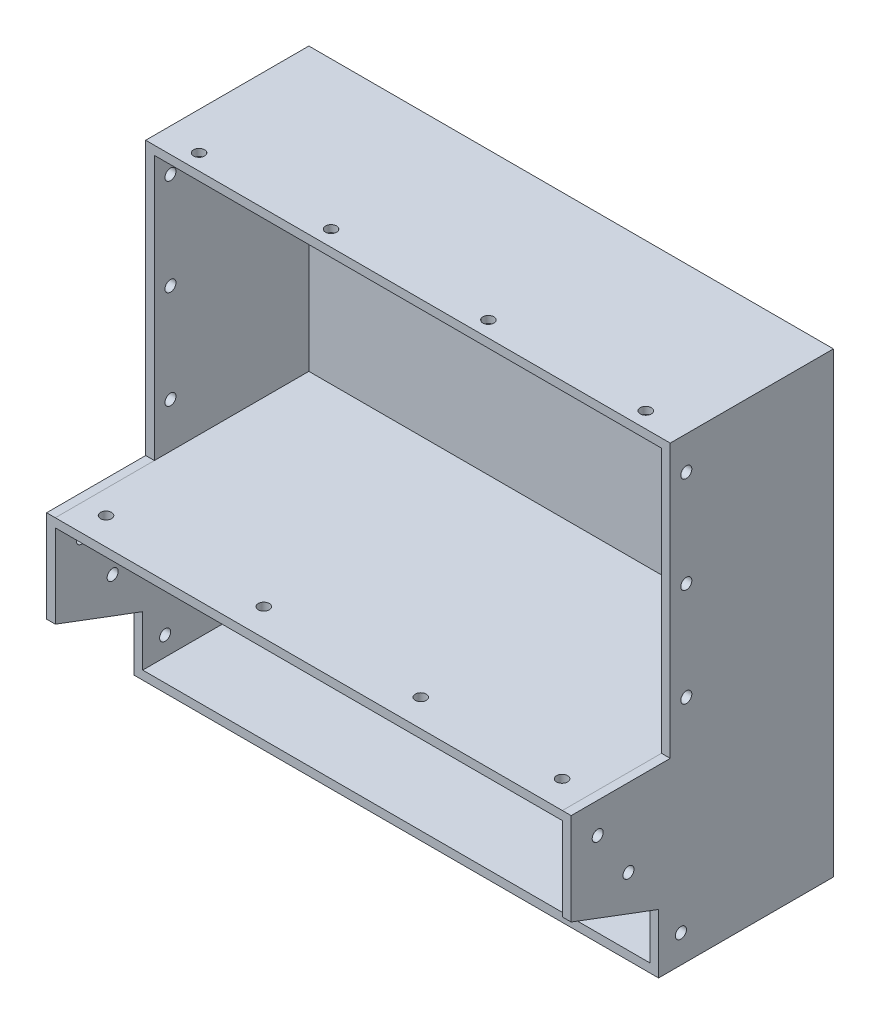
SolidWorks part; units mm, degrees
material "Custom Plastic"
ref_plane "X-Y Datum" through (0, 0, 0) normal (0, 0, 1) x (1, 0, 0)
ref_plane "X-Z Datum" through (0, 0, 0) normal (0, 1, 0) x (1, 0, 0)
ref_plane "Y-Z Datum" through (0, 0, 0) normal (1, 0, 0) x (0, 0, -1)
sketch "Sketch1" plane through (0, 0, 0) normal (0, 0, 1) x (1, 0, 0)
  line L1 (-95.25, -83.058) -> (95.25, -83.058)
  line L2 (-95.25, -83.058) -> (-95.25, 83.058)
  line L3 (-95.25, 83.058) -> (95.25, 83.058)
  line L4 (95.25, -83.058) -> (95.25, 83.058)
  line L5 (-95.25, -83.058) -> (95.25, 83.058) construction
  line L6 (-95.25, 83.058) -> (95.25, -83.058) construction
  point P0 (0, 0)
  dimension "D1" = 166.116
  dimension "D2" = 190.5
extrude "Boss-Extrude1" add sketch "Sketch1" along normal blind 95.25
sketch "Sketch3" plane through (0, 0, 95.25) normal (0, 0, 1) x (1, 0, 0)
  line L0 (-92.075, -49.9618) -> (92.075, -49.9618)
  line L1 (92.075, -61.8913) -> (95.25, -61.8913)
  line L2 (-92.075, -61.8913) -> (92.075, -61.8913)
  line L3 (95.25, -83.058) -> (95.25, 83.058) construction
  line L4 (-92.075, -61.8913) -> (-92.075, -79.883)
  line L5 (-95.25, -49.9618) -> (-95.25, -61.8913)
  line L6 (92.075, -61.8913) -> (92.075, -79.883)
  line L7 (-95.25, 83.058) -> (-95.25, -83.058) construction
  line L8 (-122.0928, 3.2687) -> (-122.1486, 3.2687)
  line L9 (92.075, -79.883) -> (76.2531, -79.883)
  line L13 (-95.25, 32.8917) -> (-92.075, 32.8917)
  line L15 (-122.0786, -16.0951) -> (-122.1486, -16.0951)
  line L17 (95.25, -49.9618) -> (92.075, -49.9618)
  line L18 (-92.075, -79.883) -> (76.2531, -79.883)
  line L21 (-92.075, -49.9618) -> (-95.25, -49.9618)
  line L23 (-81.0858, 79.883) -> (83.8833, 79.883)
  line L25 (-81.0858, 79.883) -> (-92.075, 79.883)
  line L26 (-92.075, 79.883) -> (-92.075, -16.0951)
  line L28 (95.25, 48.6627) -> (92.075, 48.6627)
  line L30 (83.8833, 79.883) -> (92.075, 79.883)
  line L31 (92.075, 79.883) -> (92.075, -16.0951)
  line L33 (-92.075, -16.0951) -> (92.075, -16.0951)
  line L34 (95.25, -49.9618) -> (95.25, -61.8913)
  line L35 (-95.25, -61.8913) -> (-92.075, -61.8913)
extrude "Cut-Extrude1" cut sketch "Sketch3" against normal blind 92.075 contours L23 region at (0, 31.8939, 95.25)
sketch "Sketch15" plane through (0, 0, 95.25) normal (0, 0, 1) x (1, 0, 0)
  line L1 (-95.25, 83.058) -> (-95.25, -83.058) construction
  line L3 (95.25, -83.058) -> (95.25, 83.058) construction
  line L4 (95.25, -16.1093) -> (95.25, 83.058)
  line L5 (95.25, 83.058) -> (-95.25, 83.058)
  line L6 (-95.25, 83.058) -> (-95.25, -16.1093)
  line L10 (95.25, -16.1093) -> (92.075, -16.0951)
  line L11 (92.075, -16.0951) -> (92.075, 79.883)
  line L12 (92.075, 79.883) -> (-92.075, 79.883)
  line L13 (-92.075, 79.883) -> (-92.075, -16.0951)
  line L14 (-92.075, -16.0951) -> (92.075, -16.0951) construction
  line L15 (-92.075, 79.883) -> (-92.075, -16.0951) construction
  line L16 (-95.25, -16.1093) -> (-92.075, -16.0951)
extrude "Cut-Extrude5" cut sketch "Sketch15" against normal blind 35.9842
sketch "Sketch17" plane through (0, 0, 95.25) normal (0, 0, 1) x (1, 0, 0)
  line L0 (-95.25, -49.5836) -> (-95.25, -83.058)
  line L2 (-95.25, -83.058) -> (95.25, -83.058)
  line L3 (-95.25, -16.1093) -> (-95.25, -83.058) construction
  line L4 (95.25, -83.058) -> (95.25, -16.1093) construction
  line L5 (95.25, -83.058) -> (95.25, -49.5836)
  line L6 (-95.25, -49.5836) -> (95.25, -49.5836)
extrude "Cut-Extrude6" cut sketch "Sketch17" against normal blind 31.75
sketch "Sketch18" plane through (-95.25, 0, 0) normal (-1, 0, 0) x (0, 0, 1)
  line L0 (63.5, -49.5836) -> (63.5, -61.5061)
  line L1 (63.5, -49.5836) -> (63.5, -83.058) construction
  line L2 (63.5, -61.5061) -> (95.25, -49.5836)
  line L3 (95.25, -49.5836) -> (63.5, -49.5836)
extrude "Boss-Extrude8" add sketch "Sketch18" against normal blind 190.5
sketch "Sketch19" plane through (0, 0, 95.25) normal (0, 0, 1) x (1, 0, 0)
  line L0 (-92.075, -19.2701) -> (-92.075, -49.5836)
  line L2 (95.25, -49.5836) -> (-95.25, -49.5836) construction
  line L4 (92.075, -19.2701) -> (92.075, -49.5836)
  line L6 (92.075, -49.5836) -> (-92.075, -49.5836)
  line L8 (-92.075, -19.2701) -> (92.075, -19.2701)
extrude "Cut-Extrude7" cut sketch "Sketch19" against normal blind 92.075
sketch "Sketch20" plane through (0, -74.8032, 28.0894) normal (0, -0.9362, 0.3515) x (1, 0, 0)
  line L2 (-92.075, -3.8019) -> (-92.075, 82.3961) construction
  line L4 (-92.075, 71.7396) -> (92.075, 71.7396) construction
  line L6 (-92.075, 71.7396) -> (92.075, 71.7396)
  line L12 (92.075, -3.8019) -> (92.075, 82.3961) construction
  line L13 (95.25, 71.7396) -> (92.075, 71.7396) construction
  line L15 (-92.075, 71.7396) -> (-92.075, 37.8249)
  line L16 (95.25, 37.8249) -> (-95.25, 37.8249) construction
  line L17 (92.075, 71.7396) -> (92.075, 37.8249)
  line L18 (92.075, 37.8249) -> (-92.075, 37.8249)
extrude "Cut-Extrude8" cut sketch "Sketch20" against normal blind 13.175
sketch "Sketch21" plane through (0, 0, 63.5) normal (0, 0, 1) x (1, 0, 0)
  line L0 (-92.075, -61.5061) -> (-92.075, -49.5836)
  line L2 (-92.075, -49.5836) -> (92.075, -49.5836)
  line L4 (92.075, -49.5836) -> (92.075, -61.5061)
  line L6 (-92.075, -61.5061) -> (-92.075, -79.883)
  line L7 (-92.075, -79.883) -> (92.075, -79.883)
  line L8 (92.075, -79.883) -> (92.075, -61.5061)
extrude "Cut-Extrude9" cut sketch "Sketch21" against normal blind 60.325
sketch "Sketch23" plane through (0, -83.058, 0) normal (0, -1, 0) x (1, 0, 0)
  circle A4 centre (-83.3197, 53.848) radius 2
  circle A5 centre (-26.4237, 53.848) radius 2
  circle A6 centre (30.4723, 53.848) radius 2
  circle A7 centre (82.2883, 53.848) radius 2
extrude "Cut-Extrude10" cut sketch "Sketch23" against normal blind 2.54
sketch "Sketch24" plane through (0, 83.058, 0) normal (0, 1, 0) x (1, 0, 0)
  line L0 (80.6562, -53.5508) -> (-86.3243, -53.5508) construction
  line L1 (95.25, -59.2658) -> (-95.25, -59.2658) construction
  circle A0 centre (80.6562, -53.5508) radius 2
  circle A3 centre (23.5062, -53.5508) radius 2
  circle A4 centre (-33.6438, -53.5508) radius 2
  circle A7 centre (-81.5688, -53.5508) radius 2
  dimension "D1" = 5.715
extrude "Cut-Extrude11" cut sketch "Sketch24" against normal blind 2.54
sketch "Sketch25" plane through (95.25, 0, 0) normal (1, 0, 0) x (0, 0, -1)
  circle A0 centre (-53.4238, 70.993) radius 2
  circle A1 centre (-53.4238, 35.941) radius 2
  circle A4 centre (-53.4238, 0.889) radius 2 [skipped]
  circle A6 centre (-53.4238, 0.2178) radius 2
  dimension "D2" = 3
extrude "Cut-Extrude12" cut sketch "Sketch25" against normal through all
sketch "Sketch26" plane through (0, -16.0951, 0) normal (0, 1, 0) x (1, 0, 0)
  line L1 (92.075, -59.2658) -> (92.075, -95.25) construction
  line L2 (92.075, -63.7108) -> (-92.075, -63.7108)
  line L3 (-92.075, -59.2658) -> (-92.075, -95.25) construction
  line L5 (-92.075, -79.375) -> (92.075, -79.375)
sketch "Sketch27" plane through (0, -16.0951, 0) normal (0, 1, 0) x (1, 0, 0)
  circle A0 centre (82.042, -85.344) radius 2
  circle A8 centre (30.734, -85.344) radius 2
  circle A11 centre (-26.2686, -85.344) radius 2
  circle A12 centre (-83.566, -85.344) radius 2
extrude "Cut-Extrude13" cut sketch "Sketch27" against normal blind 3.175
sketch "Sketch28" plane through (95.25, 0, 0) normal (1, 0, 0) x (0, 0, -1)
  circle A0 centre (-55.372, -72.898) radius 2
  circle A1 centre (-74.422, -44.3819) radius 2
  circle A2 centre (-85.598, -27.204) radius 2
extrude "Cut-Extrude15" cut sketch "Sketch28" against normal through all
